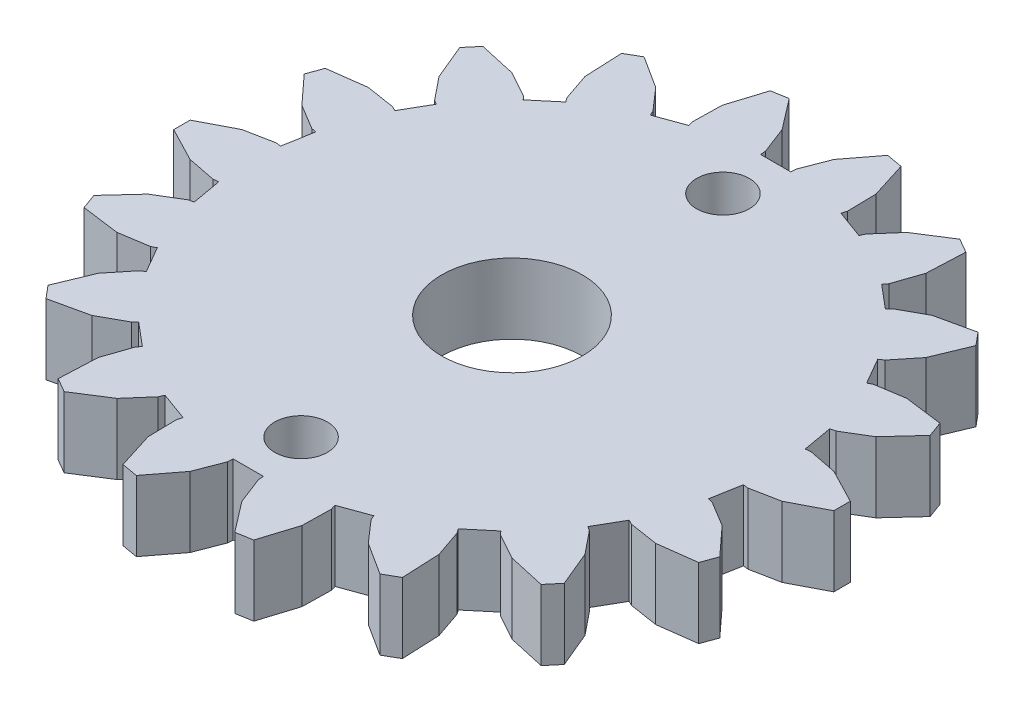
SolidWorks part; units mm, degrees
material "Acrylic (Medium-high impact)"
ref_plane "Front Plane" through (0, 0, 0) normal (0, 0, 1) x (1, 0, 0)
ref_plane "Top Plane" through (0, 0, 0) normal (0, 1, 0) x (1, 0, 0)
ref_plane "Right Plane" through (0, 0, 0) normal (1, 0, 0) x (0, 0, -1)
sketch "Sketch2" plane through (0, 0, 0) normal (0, 1, 0) x (1, 0, 0)
  line L0 (35.8813, 21.7468) -> (36.1737, 21.7812)
  line L1 (36.1737, 21.7812) -> (37.7983, 21.4625)
  line L2 (37.7983, 21.4625) -> (39.7347, 20.4569)
  line L3 (39.7347, 20.4569) -> (39.7347, 19.5217)
  line L4 (39.7347, 19.5217) -> (37.7983, 18.5162)
  line L5 (37.7983, 18.5162) -> (36.1737, 18.1975)
  line L6 (36.1737, 18.1975) -> (35.8813, 18.2318)
  line L7 (35.8813, 18.2318) -> (35.5825, 16.5374)
  line L8 (35.5825, 16.5374) -> (35.8691, 16.4697)
  line L9 (35.8691, 16.4697) -> (37.2866, 15.6147)
  line L10 (37.2866, 15.6147) -> (38.7625, 14.0073)
  line L11 (38.7625, 14.0073) -> (38.4426, 13.1285)
  line L12 (38.4426, 13.1285) -> (36.2788, 12.846)
  line L13 (36.2788, 12.846) -> (34.6433, 13.1021)
  line L14 (34.6433, 13.1021) -> (34.3803, 13.2344)
  line L15 (34.3803, 13.2344) -> (33.5201, 11.7443)
  line L16 (33.5201, 11.7443) -> (33.7661, 11.5828)
  line L17 (33.7661, 11.5828) -> (34.8057, 10.2943)
  line L18 (34.8057, 10.2943) -> (35.6429, 8.2793)
  line L19 (35.6429, 8.2793) -> (35.0417, 7.5627)
  line L20 (35.0417, 7.5627) -> (32.9117, 8.0374)
  line L21 (32.9117, 8.0374) -> (31.4625, 8.8373)
  line L22 (31.4625, 8.8373) -> (31.2606, 9.0516)
  line L23 (31.2606, 9.0516) -> (29.9425, 7.9456)
  line L24 (29.9425, 7.9456) -> (30.1186, 7.7096)
  line L25 (30.1186, 7.7096) -> (30.6548, 6.1434)
  line L26 (30.6548, 6.1434) -> (30.7523, 3.9636)
  line L27 (30.7523, 3.9636) -> (29.9423, 3.4959)
  line L28 (29.9423, 3.4959) -> (28.1031, 4.6703)
  line L29 (28.1031, 4.6703) -> (27.0148, 5.9177)
  line L30 (27.0148, 5.9177) -> (26.8984, 6.1882)
  line L31 (26.8984, 6.1882) -> (25.2816, 5.5997)
  line L32 (25.2816, 5.5997) -> (25.3663, 5.3177)
  line L33 (25.3663, 5.3177) -> (25.3345, 3.6625)
  line L34 (25.3345, 3.6625) -> (24.6806, 1.5808)
  line L35 (24.6806, 1.5808) -> (23.7594, 1.4184)
  line L36 (23.7594, 1.4184) -> (22.4329, 3.1508)
  line L37 (22.4329, 3.1508) -> (21.837, 4.6954)
  line L38 (21.837, 4.6954) -> (21.82, 4.9893)
  line L39 (21.82, 4.9893) -> (20.0995, 4.9893)
  line L40 (20.0995, 4.9893) -> (20.0826, 4.6954)
  line L41 (20.0826, 4.6954) -> (19.4866, 3.1508)
  line L42 (19.4866, 3.1508) -> (18.1601, 1.4184)
  line L43 (18.1601, 1.4184) -> (17.239, 1.5808)
  line L44 (17.239, 1.5808) -> (16.5851, 3.6625)
  line L45 (16.5851, 3.6625) -> (16.5532, 5.3177)
  line L46 (16.5532, 5.3177) -> (16.6379, 5.5997)
  line L47 (16.6379, 5.5997) -> (15.0211, 6.1882)
  line L48 (15.0211, 6.1882) -> (14.9047, 5.9177)
  line L49 (14.9047, 5.9177) -> (13.8164, 4.6703)
  line L50 (13.8164, 4.6703) -> (11.9772, 3.4959)
  line L51 (11.9772, 3.4959) -> (11.1673, 3.9636)
  line L52 (11.1673, 3.9636) -> (11.2648, 6.1434)
  line L53 (11.2648, 6.1434) -> (11.8009, 7.7096)
  line L54 (11.8009, 7.7096) -> (11.9771, 7.9456)
  line L55 (11.9771, 7.9456) -> (10.659, 9.0516)
  line L56 (10.659, 9.0516) -> (10.457, 8.8373)
  line L57 (10.457, 8.8373) -> (9.0078, 8.0374)
  line L58 (9.0078, 8.0374) -> (6.8778, 7.5627)
  line L59 (6.8778, 7.5627) -> (6.2766, 8.2793)
  line L60 (6.2766, 8.2793) -> (7.1138, 10.2943)
  line L61 (7.1138, 10.2943) -> (8.1535, 11.5828)
  line L62 (8.1535, 11.5828) -> (8.3995, 11.7443)
  line L63 (8.3995, 11.7443) -> (7.5392, 13.2344)
  line L64 (7.5392, 13.2344) -> (7.2762, 13.1021)
  line L65 (7.2762, 13.1021) -> (5.6407, 12.846)
  line L66 (5.6407, 12.846) -> (3.477, 13.1285)
  line L67 (3.477, 13.1285) -> (3.157, 14.0073)
  line L68 (3.157, 14.0073) -> (4.633, 15.6147)
  line L69 (4.633, 15.6147) -> (6.0505, 16.4697)
  line L70 (6.0505, 16.4697) -> (6.3371, 16.5374)
  line L71 (6.3371, 16.5374) -> (6.0382, 18.2318)
  line L72 (6.0382, 18.2318) -> (5.7459, 18.1975)
  line L73 (5.7459, 18.1975) -> (4.1213, 18.5162)
  line L74 (4.1213, 18.5162) -> (2.1848, 19.5217)
  line L75 (2.1848, 19.5217) -> (2.1848, 20.4569)
  line L76 (2.1848, 20.4569) -> (4.1213, 21.4625)
  line L77 (4.1213, 21.4625) -> (5.7459, 21.7812)
  line L78 (5.7459, 21.7812) -> (6.0382, 21.7468)
  line L79 (6.0382, 21.7468) -> (6.3371, 23.4412)
  line L80 (6.3371, 23.4412) -> (6.0505, 23.5089)
  line L81 (6.0505, 23.5089) -> (4.633, 24.364)
  line L82 (4.633, 24.364) -> (3.157, 25.9714)
  line L83 (3.157, 25.9714) -> (3.477, 26.8502)
  line L84 (3.477, 26.8502) -> (5.6407, 27.1327)
  line L85 (5.6407, 27.1327) -> (7.2762, 26.8766)
  line L86 (7.2762, 26.8766) -> (7.5392, 26.7443)
  line L87 (7.5392, 26.7443) -> (8.3995, 28.2344)
  line L88 (8.3995, 28.2344) -> (8.1535, 28.3959)
  line L89 (8.1535, 28.3959) -> (7.1138, 29.6843)
  line L90 (7.1138, 29.6843) -> (6.2766, 31.6994)
  line L91 (6.2766, 31.6994) -> (6.8778, 32.416)
  line L92 (6.8778, 32.416) -> (9.0078, 31.9413)
  line L93 (9.0078, 31.9413) -> (10.457, 31.1414)
  line L94 (10.457, 31.1414) -> (10.659, 30.9271)
  line L95 (10.659, 30.9271) -> (11.9771, 32.0331)
  line L96 (11.9771, 32.0331) -> (11.8009, 32.2691)
  line L97 (11.8009, 32.2691) -> (11.2648, 33.8353)
  line L98 (11.2648, 33.8353) -> (11.1673, 36.0151)
  line L99 (11.1673, 36.0151) -> (11.9772, 36.4828)
  line L100 (11.9772, 36.4828) -> (13.8164, 35.3084)
  line L101 (13.8164, 35.3084) -> (14.9047, 34.0609)
  line L102 (14.9047, 34.0609) -> (15.0211, 33.7904)
  line L103 (15.0211, 33.7904) -> (16.6379, 34.379)
  line L104 (16.6379, 34.379) -> (16.5532, 34.661)
  line L105 (16.5532, 34.661) -> (16.5851, 36.3161)
  line L106 (16.5851, 36.3161) -> (17.239, 38.3979)
  line L107 (17.239, 38.3979) -> (18.1601, 38.5603)
  line L108 (18.1601, 38.5603) -> (19.4866, 36.8278)
  line L109 (19.4866, 36.8278) -> (20.0826, 35.2833)
  line L110 (20.0826, 35.2833) -> (20.0995, 34.9893)
  line L111 (20.0995, 34.9893) -> (21.82, 34.9893)
  line L112 (21.82, 34.9893) -> (21.837, 35.2833)
  line L113 (21.837, 35.2833) -> (22.4329, 36.8278)
  line L114 (22.4329, 36.8278) -> (23.7594, 38.5603)
  line L115 (23.7594, 38.5603) -> (24.6806, 38.3979)
  line L116 (24.6806, 38.3979) -> (25.3345, 36.3161)
  line L117 (25.3345, 36.3161) -> (25.3663, 34.661)
  line L118 (25.3663, 34.661) -> (25.2816, 34.379)
  line L119 (25.2816, 34.379) -> (26.8984, 33.7904)
  line L120 (26.8984, 33.7904) -> (27.0148, 34.0609)
  line L121 (27.0148, 34.0609) -> (28.1031, 35.3084)
  line L122 (28.1031, 35.3084) -> (29.9423, 36.4828)
  line L123 (29.9423, 36.4828) -> (30.7523, 36.0151)
  line L124 (30.7523, 36.0151) -> (30.6548, 33.8353)
  line L125 (30.6548, 33.8353) -> (30.1186, 32.2691)
  line L126 (30.1186, 32.2691) -> (29.9425, 32.0331)
  line L127 (29.9425, 32.0331) -> (31.2606, 30.9271)
  line L128 (31.2606, 30.9271) -> (31.4625, 31.1414)
  line L129 (31.4625, 31.1414) -> (32.9117, 31.9413)
  line L130 (32.9117, 31.9413) -> (35.0417, 32.416)
  line L131 (35.0417, 32.416) -> (35.6429, 31.6994)
  line L132 (35.6429, 31.6994) -> (34.8057, 29.6843)
  line L133 (34.8057, 29.6843) -> (33.7661, 28.3959)
  line L134 (33.7661, 28.3959) -> (33.5201, 28.2344)
  line L135 (33.5201, 28.2344) -> (34.3803, 26.7443)
  line L136 (34.3803, 26.7443) -> (34.6433, 26.8766)
  line L137 (34.6433, 26.8766) -> (36.2788, 27.1327)
  line L138 (36.2788, 27.1327) -> (38.4426, 26.8502)
  line L139 (38.4426, 26.8502) -> (38.7625, 25.9714)
  line L140 (38.7625, 25.9714) -> (37.2866, 24.364)
  line L141 (37.2866, 24.364) -> (35.8691, 23.5089)
  line L142 (35.8691, 23.5089) -> (35.5825, 23.4412)
  line L143 (35.5825, 23.4412) -> (35.8813, 21.7468)
  line L144 (20.9598, 34.9893) -> (20.9598, 4.9893) construction
  line L145 (39.7347, 19.9893) -> (2.1848, 19.9893) construction
sketch "Sketch3" plane through (0, 0, 0) normal (0, 1, 0) x (1, 0, 0)
  line L0 (20.9598, 34.9893) -> (20.9598, 4.9893) construction
  line L1 (8.2389, 19.9893) -> (32.3777, 19.9893) construction
  line L2 (39.7347, 19.9893) -> (2.1848, 19.9893) construction
  circle A0 centre (20.9598, 19.9893) radius 4
  circle A1 centre (20.9598, 31.9893) radius 1.5
  circle A2 centre (20.9598, 7.9893) radius 1.5
  dimension "D1" = 8
  dimension "D2" = 3
  dimension "D3" = 12
extrude "Boss-Extrude1" add sketch "Sketch2" along normal blind 4
extrude "Cut-Extrude1" cut sketch "Sketch3" along normal up to next
